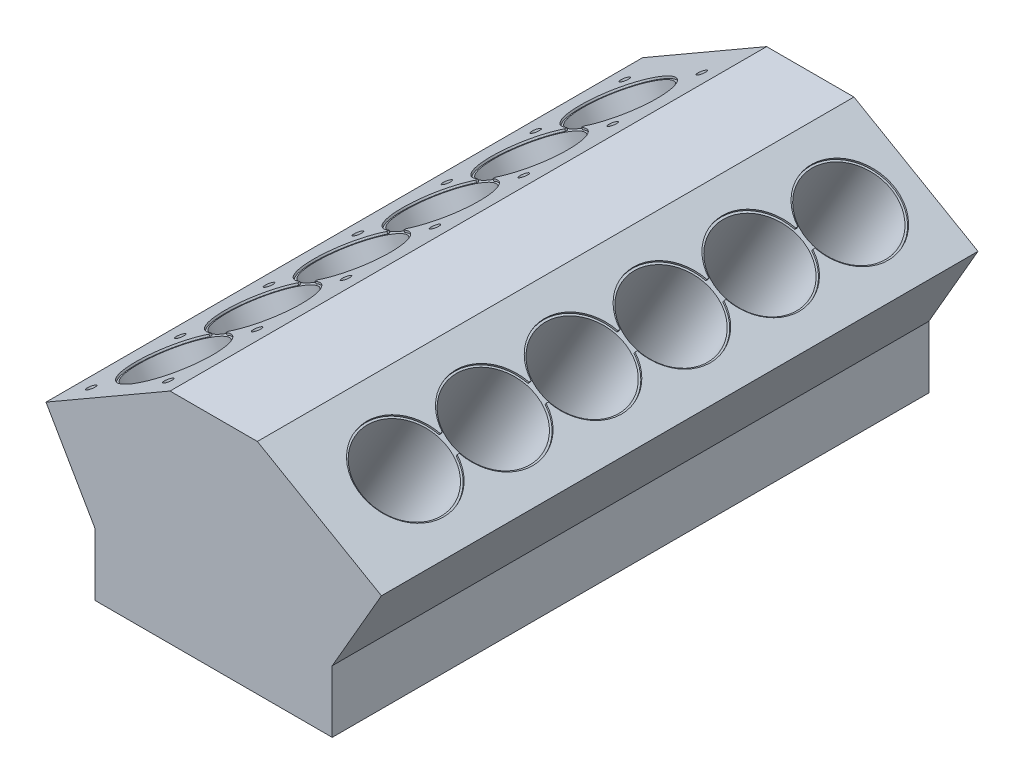
SolidWorks part; units mm, degrees
material "1060 Alloy"
ref_plane "Front Plane" through (0, 0, 0) normal (0, 0, 1) x (1, 0, 0)
ref_plane "Top Plane" through (0, 0, 0) normal (0, 1, 0) x (1, 0, 0)
ref_plane "Right Plane" through (0, 0, 0) normal (1, 0, 0) x (0, 0, -1)
sketch "Sketch1" plane through (0, 0, 0) normal (0, 0, 1) x (1, 0, 0)
  line L0 (0, 0) -> (120, 0)
  line L1 (120, 0) -> (120, 62.8461)
  line L2 (120, 62.8461) -> (169.7868, 149.0794)
  line L3 (169.7868, 149.0794) -> (44.2132, 221.5794)
  line L4 (44.2132, 221.5794) -> (0, 221.5794)
  line L5 (0, 221.5794) -> (0, 0)
  line L6 (0, 0) -> (107, 185.3294) construction
  dimension "D1" = 120
  dimension "D2" = 150
  dimension "D3" = 145
  dimension "D4" = 214
extrude "Boss-Extrude1" add sketch "Sketch1" along normal mid plane 604
mirror "Mirror1" about plane through (0, 0, 0) normal (1, 0, 0) of bodies 101
sketch "Sketch2" plane through (-107, 185.3294, 0) normal (0.5, -0.866, 0) x (-0.866, -0.5, 0)
  line L0 (72.5, 302) -> (-72.5, 302) construction
  circle A0 centre (0, 215) radius 43
  dimension "D1" = 86
  dimension "D2" = 87
extrude "Cut-Extrude1" cut sketch "Sketch2" along normal blind 154
sketch "Sketch3" plane through (107, 185.3294, 0) normal (0.5, 0.866, 0) x (0.866, -0.5, 0)
  line L0 (72.5, 302) -> (-72.5, 302) construction
  circle A0 centre (0, 235) radius 43
  dimension "D1" = 86
  dimension "D2" = 67
extrude "Cut-Extrude2" cut sketch "Sketch3" against normal blind 154
pattern_linear "LPattern1" count 6 spacing 90 along (0, 0, 1) of "Cut-Extrude1", "Cut-Extrude2"
sketch "Sketch4" plane through (-107, 185.3294, 0) normal (-0.5, 0.866, 0) x (0.866, 0.5, 0)
  line L0 (-10, 171.1252) -> (-10, -191.1398) construction
  line L1 (-10, 171.1252) -> (-10, 168.9191)
  line L2 (10, 171.1252) -> (10, 168.8143)
  line L3 (-10, 81.066) -> (-10, 78.9045)
  line L4 (10, -191.1398) -> (10, 171.1252) construction
  line L5 (0, 215) -> (0, -235) construction
  line L7 (10, 81.1708) -> (10, 78.8296)
  line L8 (-10, -8.9194) -> (-10, -11.1101)
  line L9 (10, -8.8444) -> (10, -11.1553)
  line L10 (-10, -98.9047) -> (-10, -101.1466)
  line L11 (10, -98.8595) -> (10, -101.1186)
  line L12 (-10, -188.8681) -> (-10, -191.1398)
  line L13 (10, -188.8962) -> (10, -191.1398)
  arc A0 (-10, 168.9191) -> (-10, 81.066) centre (-0.2299, 124.9925) ccw
  arc A1 (10, 81.1708) -> (10, 168.8143) centre (-0.2299, 124.9925) ccw
  arc A2 (34.641, -209.5245) -> (41.8744, -244.774) centre (0, -235) ccw construction
  arc A5 (10, -8.8444) -> (10, 78.8296) centre (-0.1644, 34.9926) ccw
  arc A6 (10, -98.8595) -> (10, -11.1553) centre (-0.099, -55.0074) ccw
  arc A7 (10, -188.8962) -> (10, -101.1186) centre (0.0615, -145.0074) ccw
  circle A11 centre (0, 215) radius 45
  arc A12 (10, 171.1252) -> (-10, 171.1252) centre (0, 215) ccw
  arc A13 (-10, 78.9045) -> (-10, -8.9194) centre (-0.1644, 34.9926) ccw
  arc A14 (-10, -11.1101) -> (-10, -98.9047) centre (-0.099, -55.0074) ccw
  arc A15 (-10, -101.1466) -> (-10, -188.8681) centre (0.0615, -145.0074) ccw
  arc A16 (-10, -191.1398) -> (10, -191.1398) centre (0, -235) ccw
  circle A17 centre (0, 125) radius 43 construction
  point P0 (-10, 215)
  point P1 (-10, -235)
  point P15 (10, 215)
  point P16 (10, -235)
  dimension "D3" = 44.9857
  dimension "D4" = 0.0615
  dimension "D5" = 0.099
  dimension "D6" = 0.1644
  dimension "D7" = 0.2299
  dimension "D8" = 43.8143
  dimension "D1" = 20
  dimension "D9" = 46.0955
  dimension "D10" = 136.1101
  dimension "D11" = 226.1186
  dimension "D2" = 2
extrude "Cut-Extrude4" cut sketch "Sketch4" against normal blind 2
sketch "Sketch6" plane through (107, 185.3294, 0) normal (0.5, 0.866, 0) x (0.866, -0.5, 0)
  line L0 (-10, 191.1252) -> (-10, -171.1398) construction
  line L1 (-10, 191.1252) -> (-10, 188.9191)
  line L2 (10, 191.1252) -> (10, 188.8143)
  line L3 (-10, 101.066) -> (-10, 98.9045)
  line L4 (10, -171.1398) -> (10, 191.1252) construction
  line L5 (0, 235) -> (0, -215) construction
  line L6 (10, 101.1708) -> (10, 98.8296)
  line L7 (-10, 11.0806) -> (-10, 8.8899)
  line L8 (10, 11.1556) -> (10, 8.8447)
  line L9 (-10, -78.9047) -> (-10, -81.1466)
  line L10 (10, -78.8595) -> (10, -81.1186)
  line L11 (-10, -168.8681) -> (-10, -171.1398)
  line L12 (10, -168.8962) -> (10, -171.1398)
  arc A0 (-10, 188.9191) -> (-10, 101.066) centre (-0.2299, 144.9925) ccw
  arc A1 (10, 101.1708) -> (10, 188.8143) centre (-0.2299, 144.9925) ccw
  arc A2 (10, 11.1556) -> (10, 98.8296) centre (-0.1644, 54.9926) ccw
  arc A3 (10, -78.8595) -> (10, 8.8447) centre (-0.099, -35.0074) ccw
  arc A4 (10, -168.8962) -> (10, -81.1186) centre (0.0615, -125.0074) ccw
  arc A5 (10, 191.1252) -> (-10, 191.1252) centre (0, 235) ccw
  arc A6 (-10, 98.9045) -> (-10, 11.0806) centre (-0.1644, 54.9926) ccw
  arc A7 (-10, 8.8899) -> (-10, -78.9047) centre (-0.099, -35.0074) ccw
  arc A8 (-10, -81.1466) -> (-10, -168.8681) centre (0.0615, -125.0074) ccw
  arc A9 (-10, -171.1398) -> (10, -171.1398) centre (0, -215) ccw
  circle A10 centre (0, 145) radius 43 construction
  dimension "D2" = 44.9857
  dimension "D3" = 45
  dimension "D1" = 20
  dimension "D4" = 0.0615
  dimension "D5" = 10
  dimension "D6" = 0.099
  dimension "D7" = 0.1644
  dimension "D8" = 0.2299
  dimension "D9" = 43.8143
  dimension "D10" = 46.1252
  dimension "D11" = 46.0955
  dimension "D12" = 136.1101
  dimension "D13" = 226.1186
  dimension "D14" = 316.1398
extrude "Cut-Extrude5" cut sketch "Sketch6" against normal blind 2
hole_wizard "M10x1.0 Tapped Hole1" positions "Sketch7" profile "Sketch9" tap size "M10x1.0" standard "DIN"
sketch "Sketch7" plane through (-107, 185.3294, 0) normal (-0.5, 0.866, 0) x (0.866, 0.5, 0)
  line L0 (0, 215.5383) -> (0, 272.7266) construction
  point P0 (45, 260)
  point P16 (-45, 260)
  point P21 (45, 170)
  point P22 (-45, 170)
  point P23 (45, 80)
  point P24 (-45, 80)
  point P25 (45, -10)
  point P26 (-45, -10)
  point P27 (45, -100)
  point P28 (-45, -100)
  point P29 (45, -190)
  point P30 (-45, -190)
  point P31 (45, -280)
  point P32 (-45, -280)
  dimension "D1" = 45
  dimension "D2" = 45
  dimension "D3" = 7
sketch "Sketch9" plane through (-68.0289, 207.8294, -260) normal (0, 0, 1) x (-0.866, -0.5, 0)
  line L0 (0, 0) -> (0, 49.7039)
  line L1 (0, 49.7039) -> (4.5, 47)
  line L2 (4.5, 47) -> (4.5, 0)
  line L5 (4.5, 0) -> (0, 0)
  line L10 (0, 49.7039) -> (-4.5, 47) construction
  line L11 (0, -6.35) -> (0, 107.95) construction
  dimension "Tap Drill Dia." = 9
  dimension "Tap Drill Depth" = 47
  dimension "Drill Angle" = 118
cosmetic thread "Hole Thread1" parameters "D1"=20, "D2"=10
cosmetic thread "Hole Thread2" parameters "D1"=20, "D2"=10
cosmetic thread "Hole Thread3" parameters "D1"=20, "D2"=10
cosmetic thread "Hole Thread4" parameters "D1"=20, "D2"=10
cosmetic thread "Hole Thread5" parameters "D1"=20, "D2"=10
cosmetic thread "Hole Thread6" parameters "D1"=20, "D2"=10
cosmetic thread "Hole Thread7" parameters "D1"=20, "D2"=10
cosmetic thread "Hole Thread8" parameters "D1"=20, "D2"=10
cosmetic thread "Hole Thread9" parameters "D1"=20, "D2"=10
cosmetic thread "Hole Thread10" parameters "D1"=20, "D2"=10
cosmetic thread "Hole Thread11" parameters "D1"=20, "D2"=10
cosmetic thread "Hole Thread12" parameters "D1"=20, "D2"=10
cosmetic thread "Hole Thread13" parameters "D1"=20, "D2"=10
cosmetic thread "Hole Thread14" parameters "D1"=20, "D2"=10
